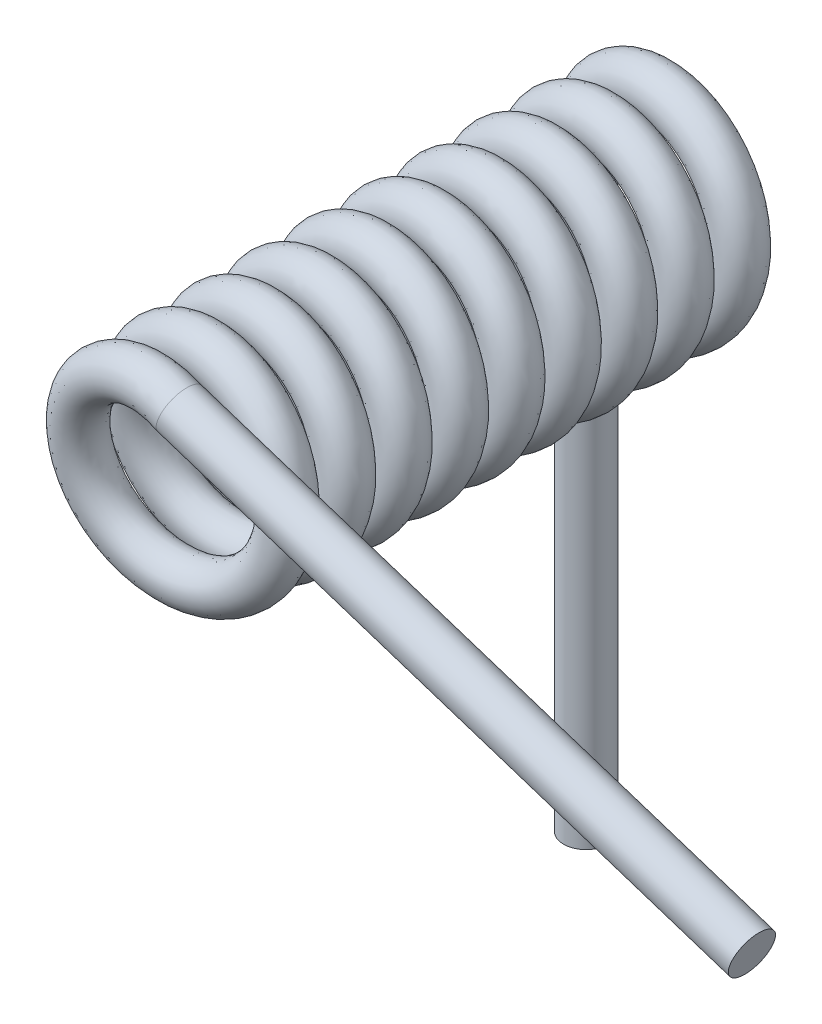
SolidWorks part; units mm, degrees
ref_plane "Front Plane" through (0, 0, 0) normal (0, 0, 1) x (1, 0, 0)
ref_plane "Top Plane" through (0, 0, 0) normal (0, 1, 0) x (1, 0, 0)
ref_plane "Right Plane" through (0, 0, 0) normal (1, 0, 0) x (0, 0, -1)
sketch "Sketch1" plane through (0, 0, 0) normal (0, 0, 1) x (1, 0, 0)
  circle A0 centre (0, 0) radius 6
  dimension "D1" = 12
curve "Helix/Spiral1" pitch 3.75 height 34.875 radius 6 left hand yes centre (0, 0, 0) axis (0, 0, 1) start towards (-1, 0, 0)
ref_plane "Plane1" through (0, 0, 0) normal (0, 1, 0) x (1, 0, 0)
sketch "Sketch2" plane through (0, 0, 0) normal (0, 1, 0) x (1, 0, 0)
  circle A0 centre (-6, 0) radius 1.5
  spline S1 degree 3 poles (-6, 0) (-6, -0.078) (-5.6842, -0.2359) (-4.3358, -0.4712) (-2.3203, -0.7069) (0.0523, -0.9426) (2.4168, -1.1782) (4.4094, -1.4139) (5.7236, -1.6495) (6.157, -1.8851) (5.6431, -2.1208) (4.2609, -2.3564) (2.2231, -2.5921) (-0.1568, -2.8277) (-2.5126, -3.0633) (-4.4818, -3.299) (-5.7613, -3.5346) (-6.1544, -3.7703) (-5.6005, -4.0059) (-4.1848, -4.2416) (-2.1252, -4.4772) (0.2613, -4.7128) (2.6077, -4.9485) (4.5528, -5.1841) (5.7974, -5.4198) (6.1499, -5.6554) (5.5562, -5.891) (4.1075, -6.1267) (2.0268, -6.3623) (-0.3658, -6.598) (-2.7021, -6.8336) (-4.6226, -7.0693) (-5.8318, -7.3049) (-6.1437, -7.5405) (-5.5103, -7.7762) (-4.029, -8.0118) (-1.9277, -8.2475) (0.4701, -8.4831) (2.7956, -8.7188) (4.691, -8.9544) (5.8646, -9.19) (6.1357, -9.4257) (5.4628, -9.6613) (3.9493, -9.897) (1.8282, -10.1326) (-0.5743, -10.3682) (-2.8884, -10.6039) (-4.7581, -10.8395) (-5.8956, -11.0752) (-6.126, -11.3108) (-5.4138, -11.5465) (-3.8685, -11.7821) (-1.728, -12.0177) (0.6783, -12.2534) (2.9803, -12.489) (4.8238, -12.7247) (5.9249, -12.9603) (6.1145, -13.1959) (5.3632, -13.4316) (3.7866, -13.6672) (1.6274, -13.9029) (-0.7822, -14.1385) (-3.0714, -14.3742) (-4.8881, -14.6098) (-5.9526, -14.8454) (-6.1012, -15.0811) (-5.311, -15.3167) (-3.7036, -15.5524) (-1.5263, -15.788) (0.8858, -16.0236) (3.1616, -16.2593) (4.9509, -16.4949) (5.9785, -16.7306) (6.0861, -16.9662) (5.2573, -17.2019) (3.6195, -17.4375) (1.4248, -17.6731) (-0.9891, -17.9088) (-3.2509, -18.1444) (-5.0124, -18.3801) (-6.0027, -18.6157) (-6.0693, -18.8514) (-5.2021, -19.087) (-3.5344, -19.3226) (-1.3229, -19.5583) (1.0922, -19.7939) (3.3392, -20.0296) (5.0724, -20.2652) (6.0252, -20.5008) (6.0508, -20.7365) (5.1454, -20.9721) (3.4483, -21.2078) (1.2206, -21.4434) (-1.1949, -21.6791) (-3.4266, -21.9147) (-5.131, -22.1503) (-6.0459, -22.386) (-6.0305, -22.6216) (-5.0872, -22.8573) (-3.3611, -23.0929) (-1.1179, -23.3285) (1.2973, -23.5642) (3.513, -23.7998) (5.1881, -24.0355) (6.0649, -24.2711) (6.0085, -24.5068) (5.0276, -24.7424) (3.273, -24.978) (1.0149, -25.2137) (-1.3994, -25.4493) (-3.5984, -25.685) (-5.2436, -25.9206) (-6.0821, -26.1563) (-5.9847, -26.3919) (-4.9665, -26.6275) (-3.184, -26.8632) (-0.9116, -27.0988) (1.501, -27.3345) (3.6827, -27.5701) (5.2977, -27.8057) (6.0976, -28.0414) (5.9592, -28.277) (4.9039, -28.5127) (3.094, -28.7483) (0.8081, -28.984) (-1.6022, -29.2196) (-3.766, -29.4552) (-5.3503, -29.6909) (-6.1113, -29.9265) (-5.932, -30.1622) (-4.84, -30.3978) (-3.0032, -30.6334) (-0.7043, -30.8691) (1.7029, -31.1047) (3.8482, -31.3404) (5.4013, -31.576) (6.1233, -31.8117) (5.9031, -32.0473) (4.7746, -32.2829) (2.9115, -32.5186) (0.6003, -32.7542) (-1.8032, -32.9899) (-3.9292, -33.2255) (-5.4507, -33.4611) (-6.1335, -33.6968) (-5.8724, -33.9324) (-4.708, -34.1681) (-2.8183, -34.4038) (-0.4984, -34.6391) (1.1079, -34.797) (1.8541, -34.875) knots 0 0 0 0 0.006757 0.013514 0.02027 0.027027 0.033784 0.040541 0.047297 0.054054 0.060811 0.067568 0.074324 0.081081 0.087838 0.094595 0.101351 0.108108 0.114865 0.121622 0.128378 0.135135 0.141892 0.148649 0.155405 0.162162 0.168919 0.175676 0.182432 0.189189 0.195946 0.202703 0.209459 0.216216 0.222973 0.22973 0.236486 0.243243 0.25 0.256757 0.263514 0.27027 0.277027 0.283784 0.290541 0.297297 0.304054 0.310811 0.317568 0.324324 0.331081 0.337838 0.344595 0.351351 0.358108 0.364865 0.371622 0.378378 0.385135 0.391892 0.398649 0.405405 0.412162 0.418919 0.425676 0.432432 0.439189 0.445946 0.452703 0.459459 0.466216 0.472973 0.47973 0.486486 0.493243 0.5 0.506757 0.513514 0.52027 0.527027 0.533784 0.540541 0.547297 0.554054 0.560811 0.567568 0.574324 0.581081 0.587838 0.594595 0.601351 0.608108 0.614865 0.621622 0.628378 0.635135 0.641892 0.648649 0.655405 0.662162 0.668919 0.675676 0.682432 0.689189 0.695946 0.702703 0.709459 0.716216 0.722973 0.72973 0.736486 0.743243 0.75 0.756757 0.763514 0.77027 0.777027 0.783784 0.790541 0.797297 0.804054 0.810811 0.817568 0.824324 0.831081 0.837838 0.844595 0.851351 0.858108 0.864865 0.871622 0.878378 0.885135 0.891892 0.898649 0.905405 0.912162 0.918919 0.925676 0.932432 0.939189 0.945946 0.952703 0.959459 0.966216 0.972973 0.97973 0.986486 0.993243 1 1 1 1 construction
  dimension "D1" = 3
sweep "Sweep1" add profiles "Sketch2" path "Helix/Spiral1"
ref_axis "Axis1" through (0, 0, -3.5303) along (0, 0, 1)
ref_plane "Plane2" through (0, 0, -1.5) normal (0, 0, 1) x (1, 0, 0)
ref_plane "Plane3" through (0, 0, 36) normal (0, 0, -1) x (-1, 0, 0)
sketch "Sketch3" plane through (0, 0, 0) normal (0, -1, 0) x (1, 0, 0)
  circle A0 centre (-6, 0) radius 1.5
  circle A1 centre (-6, 0) radius 1.5 construction
extrude "Boss-Extrude1" add sketch "Sketch3" along normal blind 40
sketch "Sketch5" plane through (0, 0, 0) normal (0.9511, -0.309, 0) x (0.309, 0.9511, 0)
  circle A0 centre (6, 34.8753) radius 1.5
  circle A3 centre (6, 34.8753) radius 1.5 construction
sketch "Sketch7" plane through (0, 0, 0) normal (0.9511, -0.309, 0) x (0.309, 0.9511, 0)
  circle A0 centre (6, 34.8753) radius 1.5
  circle A1 centre (6, 34.8753) radius 1.5 construction
extrude "Boss-Extrude3" add sketch "Sketch7" along normal blind 40
ref_axis "Axis2" through (36.2547, -5.4709, 34.8753) along (-0.9511, 0.309, 0)
sketch "Sketch8" plane through (0, -40, 0) normal (0, -1, 0) x (1, 0, 0)
  line L0 (-6, 0) -> (-7.5, 0) construction
  circle A1 centre (-6, 0) radius 1.5 construction
  spline S0 degree 3 poles (-6, 0) (-6, 0.078) (-5.6842, 0.2359) (-4.3358, 0.4712) (-2.3203, 0.7069) (0.0523, 0.9426) (2.4168, 1.1782) (4.4094, 1.4139) (5.7236, 1.6495) (6.157, 1.8851) (5.6431, 2.1208) (4.2609, 2.3564) (2.2231, 2.5921) (-0.1568, 2.8277) (-2.5126, 3.0633) (-4.4818, 3.299) (-5.7613, 3.5346) (-6.1544, 3.7703) (-5.6005, 4.0059) (-4.1848, 4.2416) (-2.1252, 4.4772) (0.2613, 4.7128) (2.6077, 4.9485) (4.5528, 5.1841) (5.7974, 5.4198) (6.1499, 5.6554) (5.5562, 5.891) (4.1075, 6.1267) (2.0268, 6.3623) (-0.3658, 6.598) (-2.7021, 6.8336) (-4.6226, 7.0693) (-5.8318, 7.3049) (-6.1437, 7.5405) (-5.5103, 7.7762) (-4.029, 8.0118) (-1.9277, 8.2475) (0.4701, 8.4831) (2.7956, 8.7188) (4.691, 8.9544) (5.8646, 9.19) (6.1357, 9.4257) (5.4628, 9.6613) (3.9493, 9.897) (1.8282, 10.1326) (-0.5743, 10.3682) (-2.8884, 10.6039) (-4.7581, 10.8395) (-5.8956, 11.0752) (-6.126, 11.3108) (-5.4138, 11.5465) (-3.8685, 11.7821) (-1.728, 12.0177) (0.6783, 12.2534) (2.9803, 12.489) (4.8238, 12.7247) (5.9249, 12.9603) (6.1145, 13.1959) (5.3632, 13.4316) (3.7866, 13.6672) (1.6274, 13.9029) (-0.7822, 14.1385) (-3.0714, 14.3742) (-4.8881, 14.6098) (-5.9526, 14.8454) (-6.1012, 15.0811) (-5.311, 15.3167) (-3.7036, 15.5524) (-1.5263, 15.788) (0.8858, 16.0236) (3.1616, 16.2593) (4.9509, 16.4949) (5.9785, 16.7306) (6.0861, 16.9662) (5.2573, 17.2019) (3.6195, 17.4375) (1.4248, 17.6731) (-0.9891, 17.9088) (-3.2509, 18.1444) (-5.0124, 18.3801) (-6.0027, 18.6157) (-6.0693, 18.8514) (-5.2021, 19.087) (-3.5344, 19.3226) (-1.3229, 19.5583) (1.0922, 19.7939) (3.3392, 20.0296) (5.0724, 20.2652) (6.0252, 20.5008) (6.0508, 20.7365) (5.1454, 20.9721) (3.4483, 21.2078) (1.2206, 21.4434) (-1.1949, 21.6791) (-3.4266, 21.9147) (-5.131, 22.1503) (-6.0459, 22.386) (-6.0305, 22.6216) (-5.0872, 22.8573) (-3.3611, 23.0929) (-1.1179, 23.3285) (1.2973, 23.5642) (3.513, 23.7998) (5.1881, 24.0355) (6.0649, 24.2711) (6.0085, 24.5068) (5.0276, 24.7424) (3.273, 24.978) (1.0149, 25.2137) (-1.3994, 25.4493) (-3.5984, 25.685) (-5.2436, 25.9206) (-6.0821, 26.1563) (-5.9847, 26.3919) (-4.9665, 26.6275) (-3.184, 26.8632) (-0.9116, 27.0988) (1.501, 27.3345) (3.6827, 27.5701) (5.2977, 27.8057) (6.0976, 28.0414) (5.9592, 28.277) (4.9039, 28.5127) (3.094, 28.7483) (0.8081, 28.984) (-1.6022, 29.2196) (-3.766, 29.4552) (-5.3503, 29.6909) (-6.1113, 29.9265) (-5.932, 30.1622) (-4.84, 30.3978) (-3.0032, 30.6334) (-0.7043, 30.8691) (1.7029, 31.1047) (3.8482, 31.3404) (5.4013, 31.576) (6.1233, 31.8117) (5.9031, 32.0473) (4.7746, 32.2829) (2.9115, 32.5186) (0.6003, 32.7542) (-1.8032, 32.9899) (-3.9292, 33.2255) (-5.4507, 33.4611) (-6.1335, 33.6968) (-5.8724, 33.9324) (-4.708, 34.1681) (-2.8183, 34.4038) (-0.4984, 34.6391) (1.1079, 34.797) (1.8541, 34.875) knots 0 0 0 0 0.006757 0.013514 0.02027 0.027027 0.033784 0.040541 0.047297 0.054054 0.060811 0.067568 0.074324 0.081081 0.087838 0.094595 0.101351 0.108108 0.114865 0.121622 0.128378 0.135135 0.141892 0.148649 0.155405 0.162162 0.168919 0.175676 0.182432 0.189189 0.195946 0.202703 0.209459 0.216216 0.222973 0.22973 0.236486 0.243243 0.25 0.256757 0.263514 0.27027 0.277027 0.283784 0.290541 0.297297 0.304054 0.310811 0.317568 0.324324 0.331081 0.337838 0.344595 0.351351 0.358108 0.364865 0.371622 0.378378 0.385135 0.391892 0.398649 0.405405 0.412162 0.418919 0.425676 0.432432 0.439189 0.445946 0.452703 0.459459 0.466216 0.472973 0.47973 0.486486 0.493243 0.5 0.506757 0.513514 0.52027 0.527027 0.533784 0.540541 0.547297 0.554054 0.560811 0.567568 0.574324 0.581081 0.587838 0.594595 0.601351 0.608108 0.614865 0.621622 0.628378 0.635135 0.641892 0.648649 0.655405 0.662162 0.668919 0.675676 0.682432 0.689189 0.695946 0.702703 0.709459 0.716216 0.722973 0.72973 0.736486 0.743243 0.75 0.756757 0.763514 0.77027 0.777027 0.783784 0.790541 0.797297 0.804054 0.810811 0.817568 0.824324 0.831081 0.837838 0.844595 0.851351 0.858108 0.864865 0.871622 0.878378 0.885135 0.891892 0.898649 0.905405 0.912162 0.918919 0.925676 0.932432 0.939189 0.945946 0.952703 0.959459 0.966216 0.972973 0.97973 0.986486 0.993243 1 1 1 1 construction
ref_point "Point1"
ref_plane "Plane7" through (-7.5, 0, 0) normal (1, 0, 0) x (0, 0, -1)
